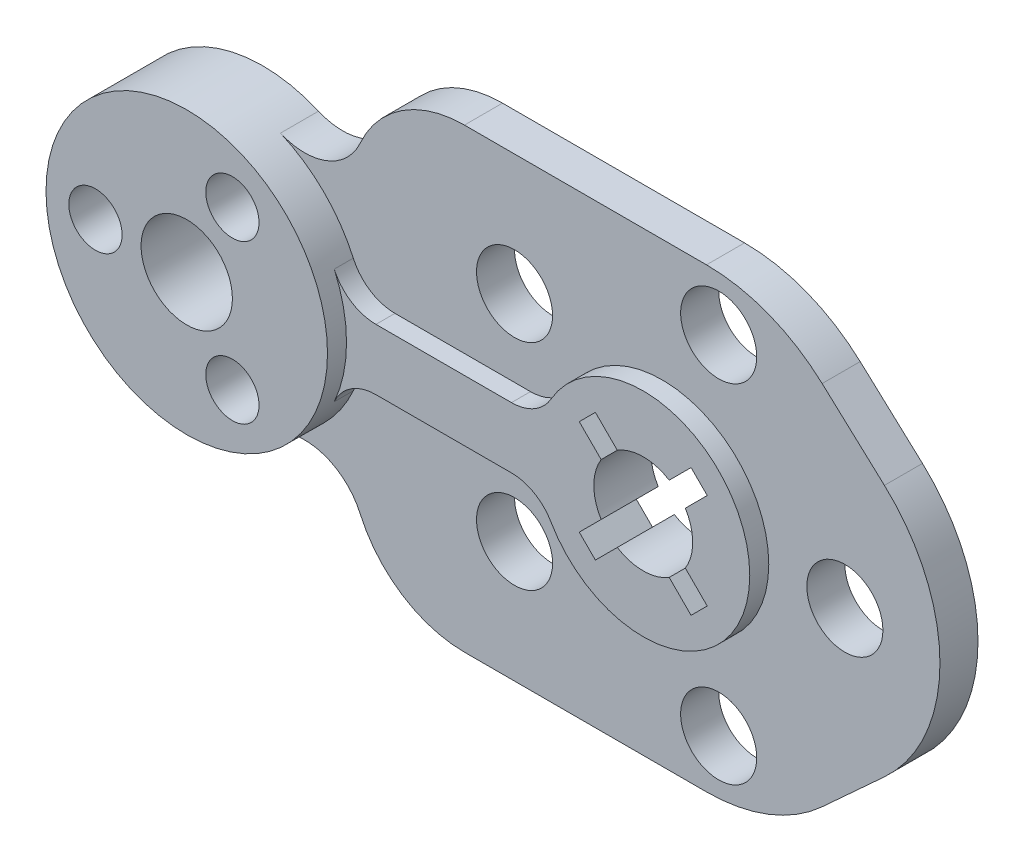
SolidWorks part; units mm, degrees
ref_plane "Спереди" through (0, 0, 0) normal (0, 0, 1) x (1, 0, 0)
ref_plane "Сверху" through (0, 0, 0) normal (0, 1, 0) x (1, 0, 0)
ref_plane "Справа" through (0, 0, 0) normal (1, 0, 0) x (0, 0, -1)
sketch "Эскиз1" plane through (0, 0, 0) normal (0, 0, 1) x (1, 0, 0)
  line L0 (37, 0) -> (-37, 0) construction
  line L1 (44.7325, 8) -> (80.359, 8)
  line L2 (115, 0) -> (115, 137.9675) construction
  line L3 (37, 0) -> (210, 0) construction
  line L4 (115, 0) -> (81.0589, 33.9411) construction
  line L5 (44.7325, -8) -> (80.359, -8)
  line L6 (100.3031, 14.6969) -> (102.4244, 16.8183)
  line L7 (100.3031, 14.6969) -> (98.1817, 12.5756)
  line L8 (98.1817, 12.5756) -> (103.9344, 6.823)
  line L9 (102.4244, 16.8183) -> (108.177, 11.0656)
  line L10 (127.5756, 16.8183) -> (121.823, 11.0656)
  line L11 (129.6969, 14.6969) -> (127.5756, 16.8183)
  line L12 (129.6969, 14.6969) -> (131.8183, 12.5756)
  line L13 (131.8183, 12.5756) -> (126.0656, 6.823)
  line L14 (131.8183, -12.5756) -> (126.0656, -6.823)
  line L15 (129.6969, -14.6969) -> (131.8183, -12.5756)
  line L16 (129.6969, -14.6969) -> (127.5756, -16.8183)
  line L17 (127.5756, -16.8183) -> (121.823, -11.0656)
  line L19 (173.4016, -33.1775) -> (157.0319, -48.1775) construction
  line L20 (115, 60) -> (63, 60)
  line L21 (126.6304, 60) -> (63, 60)
  line L23 (126.6304, -60) -> (63, -60)
  line L24 (157.0319, 48.1775) -> (173.4016, 33.1775)
  line L25 (157.0319, -48.1775) -> (173.4016, -33.1775)
  line L26 (102.4244, -16.8183) -> (108.177, -11.0656)
  line L27 (100.3031, -14.6969) -> (102.4244, -16.8183)
  line L28 (100.3031, -14.6969) -> (98.1817, -12.5756)
  line L29 (98.1817, -12.5756) -> (103.9344, -6.823)
  circle A0 centre (0, 0) radius 37
  circle A1 centre (-24, 0) radius 7
  circle A2 centre (12, 20.7846) radius 7
  circle A3 centre (12, -20.7846) radius 7
  circle A4 centre (0, 0) radius 12
  circle A5 centre (0, 0) radius 24 construction
  arc A6 (33.7776, 15.102) -> (44.7325, 8) centre (44.7325, 20) ccw
  arc A7 (90.7513, -14) -> (90.7513, 14) centre (115, 0) ccw
  arc A8 (103.9344, 6.823) -> (103.9344, -6.823) centre (115, 0) ccw
  arc A9 (80.359, 8) -> (90.7513, 14) centre (80.359, 20) ccw
  circle A10 centre (115, 0) radius 21 construction
  arc A11 (108.177, -11.0656) -> (121.823, -11.0656) centre (115, 0) ccw
  arc A12 (126.0656, -6.823) -> (126.0656, 6.823) centre (115, 0) ccw
  circle A13 centre (115, 0) radius 48 construction
  arc A14 (33.7776, -15.102) -> (44.7325, -8) centre (44.7325, -20) cw
  arc A15 (80.359, -8) -> (90.7513, -14) centre (80.359, -20) cw
  arc A16 (121.823, 11.0656) -> (108.177, 11.0656) centre (115, 0) ccw
  circle A17 centre (163, 0) radius 10
  circle A18 centre (129.8328, -45.6507) radius 10
  circle A19 centre (76.1672, -28.2137) radius 10
  circle A20 centre (76.1672, 28.2137) radius 10
  circle A21 centre (129.8328, 45.6507) radius 10
  arc A22 (157.0319, -48.1775) -> (126.6304, -60) centre (126.6304, -15) cw
  arc A23 (173.4016, -33.1775) -> (173.4016, 33.1775) centre (143, 0) ccw
  arc A24 (14.6344, 33.9829) -> (35.5844, 42.1814) centre (20.9628, 48.6781) ccw
  arc A25 (63, 60) -> (35.5844, 42.1814) centre (63, 30) ccw
  arc A26 (157.0319, 48.1775) -> (126.6304, 60) centre (126.6304, 15) ccw
  arc A27 (63, 60) -> (35.5844, 42.1814) centre (63, 30) ccw
  arc A28 (63, -60) -> (35.5844, -42.1814) centre (63, -30) cw
  arc A29 (14.6344, -33.9829) -> (35.5844, -42.1814) centre (20.9628, -48.6781) cw
  point P13 (0, 0)
  point P16 (0, 0)
  point P19 (0, 0)
  point P33 (188, 0)
  point P64 (115, 0)
  point P77 (142, 60)
  point P90 (115, 0)
  dimension "D1" = 74
  dimension "D2" = 14
  dimension "D4" = 48
  dimension "D6" = 24
  dimension "D8" = 12
  dimension "D9" = 115
  dimension "D10" = 12
  dimension "D11" = 6
  dimension "D12" = 28
  dimension "D15" = 42
  dimension "D18" = 20
  dimension "D17" = 5
  dimension "D19" = 96
  dimension "D20" = 120
  dimension "D22" = 95
  dimension "D24" = 30
  dimension "D25" = 16
  dimension "D27" = 45
  dimension "D28" = 45
  dimension "D14" = 13
  dimension "D21" = 73
  dimension "D3" = 24
  dimension "D5" = 24
  dimension "D7" = 8
  dimension "D13" = 45
  dimension "D16" = 52
  dimension "D23" = 85
  dimension "D26" = 79
extrude "Бобышка-Вытянуть1" add sketch "Эскиз1" along normal blind 10 contours A0 A29 A28 L23 A22 L25 A23 L24 A26 L21 L20 A25 A24 A6 L1 A9 A7 A15 L5 A14 A17 A18 A19 A20 A21 region at (39.3517, 11.7, 0)
extrude "Бобышка-Вытянуть2" add sketch "Эскиз1<3>" along normal blind 20 contours A0 A4 A3 A2 A1 region at (35.162, 7.5026, 0)
sketch "Эскиз1<3>" plane through (0, 0, 0) normal (0, 0, 1) x (1, 0, 0) same geometry as "Эскиз1"
extrude "Бобышка-Вытянуть3" add sketch "Эскиз1<4>" along normal blind 15 contours L5 A15 A7 A9 L1 A6 A0 A14 A16 L10 L11 L12 L13 A12 L14 L15 L16 L17 A11 L26 L27 L28 L29 A8 L8 L7 L6 L9 region at (97.5176, 0, 0)
sketch "Эскиз1<4>" plane through (0, 0, 0) normal (0, 0, 1) x (1, 0, 0) same geometry as "Эскиз1"
